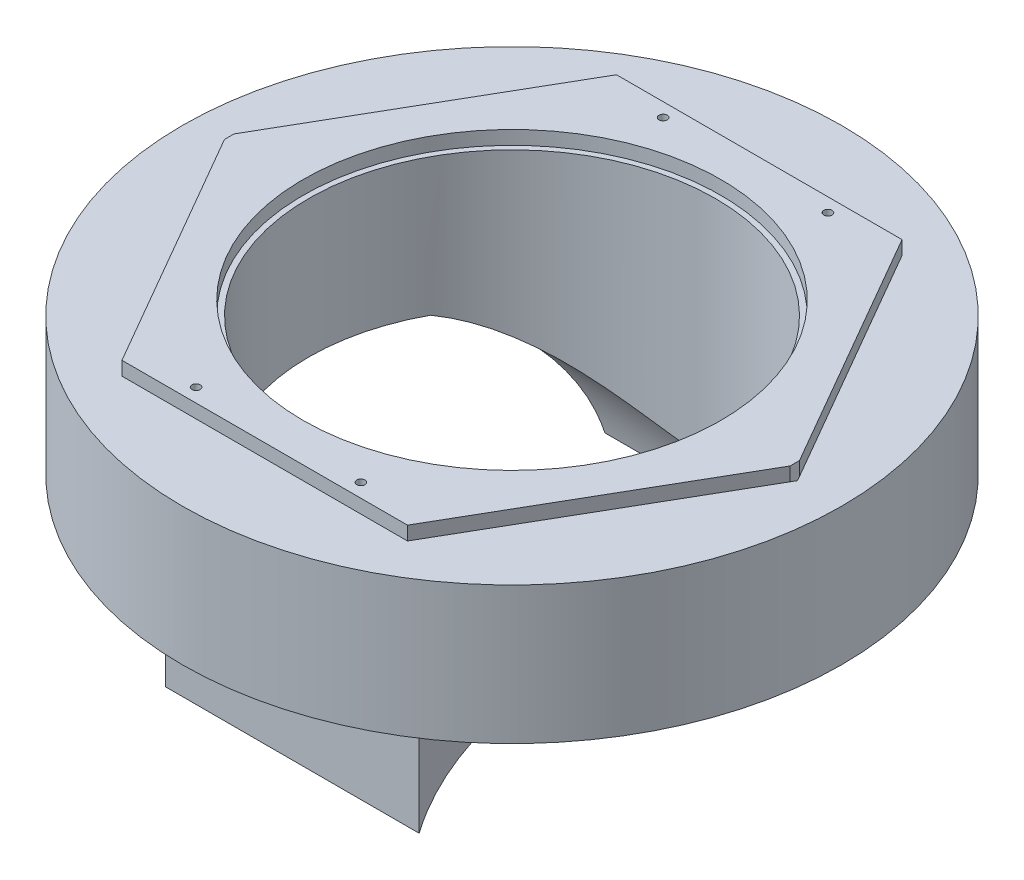
SolidWorks part; units mm, degrees
ref_plane "Front Plane" through (0, 0, 0) normal (0, 0, 1) x (1, 0, 0)
ref_plane "Top Plane" through (0, 0, 0) normal (0, 1, 0) x (1, 0, 0)
ref_plane "Right Plane" through (0, 0, 0) normal (1, 0, 0) x (0, 0, -1)
sketch "Sketch1" plane through (0, 0, 0) normal (0, 1, 0) x (1, 0, 0)
  line L1 (103.923, 0) -> (51.9615, 90)
  line L2 (51.9615, 90) -> (-51.9615, 90)
  line L3 (-51.9615, 90) -> (-103.923, 0)
  line L4 (-103.923, 0) -> (-51.9615, -90)
  line L5 (-51.9615, -90) -> (51.9615, -90)
  line L6 (51.9615, -90) -> (103.923, 0)
  circle A0 centre (0, 0) radius 76
  arc A1 (28.5424, 85.3542) -> (-28.5424, 85.3542) centre (0, 0) ccw construction
  circle A2 centre (30, 85) radius 1.5
  circle A3 centre (-30, 85) radius 1.5
  circle A4 centre (30, -85) radius 1.5
  circle A5 centre (-30, -85) radius 1.5
  arc A6 (-31.357, 84.3608) -> (-31.357, -84.3608) centre (0, 0) ccw construction
  arc A7 (-28.5424, -85.3542) -> (28.5424, -85.3542) centre (0, 0) ccw construction
  arc A8 (31.357, -84.3608) -> (31.357, 84.3608) centre (0, 0) ccw construction
  dimension "D1" = 152
  dimension "D9" = 3
  dimension "D10" = 3
  dimension "D11" = 3
  dimension "D12" = 3
  dimension "D2" = 180
extrude "Boss-Extrude1" add sketch "Sketch1" along normal blind 5
sketch "Sketch2" plane through (0, 0, 0) normal (0, -1, 0) x (1, 0, 0)
  circle A8 centre (0, 0) radius 74
  circle A11 centre (0, 0) radius 120
  dimension "D1" = 148
  dimension "D2" = 240
extrude "Boss-Extrude2" add sketch "Sketch2" along normal blind 50
sketch "Sketch3" plane through (0, -50, 0) normal (0, -1, 0) x (1, 0, 0)
  line L0 (0, 74) -> (0, 80)
  line L1 (0, -74) -> (0, -80)
  line L4 (65, 35.3695) -> (65, 47.4167)
  line L5 (65, -35.3695) -> (65, -47.4167)
  line L6 (-65, 35.3695) -> (-65, 47.4167)
  line L7 (-65, -35.3695) -> (-65, -47.4167)
  line L8 (-46.188, 80) -> (-65, 47.4167)
  line L10 (-46.188, 80) -> (46.188, 80)
  line L11 (46.188, 80) -> (65, 47.4167)
  line L13 (0, -80) -> (46.188, -80)
  line L14 (46.188, -80) -> (65, -47.4167)
  line L16 (0, -80) -> (-46.188, -80)
  line L17 (-46.188, -80) -> (-65, -47.4167)
  arc A0 (65, 35.3695) -> (-65, 35.3695) centre (0, 0) ccw
  arc A1 (-65, -35.3695) -> (65, -35.3695) centre (0, 0) ccw
  dimension "D1" = 80
  dimension "D2" = 80
extrude "Boss-Extrude3" add sketch "Sketch3" along normal blind 50 contours L5 L1 | L4 L0 | L6 L0 | L7 L1 region at (-37.9821, -50, 67.6199) region at (37.9821, -50, 67.6199) region at (37.9821, -50, -67.6199) region at (-37.9821, -50, -67.6199)
fillet "Fillet1" radius 30 rebuild error yes
fillet "Fillet2" radius 30 rebuild error yes
sketch "Sketch4" plane through (0, 5, 0) normal (0, 1, 0) x (1, 0, 0)
  line L0 (-103.923, 0) -> (-102.923, 0)
  line L1 (-102.923, 0) -> (-102.923, 15.9835)
  line L2 (-102.923, 15.9835) -> (-112.2362, 15.9835)
  line L3 (-112.2362, 15.9835) -> (-112.2362, -18.5005)
  line L4 (-112.2362, -18.5005) -> (-102.923, -18.5005)
  line L5 (-102.923, -18.5005) -> (-102.923, 0)
  line L6 (103.923, 0) -> (102.923, 0)
  line L7 (102.923, 0) -> (102.923, 26.8069)
  line L8 (102.923, 26.8069) -> (114.2499, 26.8069)
  line L9 (114.2499, 26.8069) -> (114.2499, -39.3923)
  line L10 (114.2499, -39.3923) -> (102.923, -39.3923)
  line L11 (102.923, -39.3923) -> (102.923, 0)
  line M5 (51.9615, -90) -> (103.923, 0)
  line M6 (103.923, 0) -> (51.9615, 90)
  line M8 (-51.9615, 90) -> (-103.923, 0)
  line M9 (-103.923, 0) -> (-51.9615, -90)
  dimension "D1" = 1
  dimension "D2" = 1
extrude "Cut-Extrude2" cut sketch "Sketch4" against normal blind 10 contours L0 L1 M8 | L5 L0 M9 | L11 L6 M5 | L7 L6 M6 region at (-103.2564, 5, -0.5774) region at (-103.2564, 5, 0.5774) region at (103.2564, 5, 0.5774) region at (103.2564, 5, -0.5774)
sketch "Sketch5" plane through (102.923, 0, 0) normal (1, 0, 0) x (0, 0, -1)
  line L0 (-35.3695, -50) -> (35.3695, -50)
  line L1 (80, -100) -> (-80, -100)
  arc A0 (-80, -100) -> (-35.3695, -50) centre (-11.8356, -115.9254) cw
  arc A1 (80, -100) -> (35.3695, -50) centre (11.8356, -115.9254) ccw
  dimension "D1" = 70
  dimension "D2" = 70
extrude "Cut-Extrude3" cut sketch "Sketch5" against normal blind 211
fillet "Fillet3" radius 50 rebuild error yes
sketch "Sketch6" plane through (0, 0, 0) normal (0, -1, 0) x (1, 0, 0)
  line L0 (51.9615, 90) -> (153.8846, 90)
